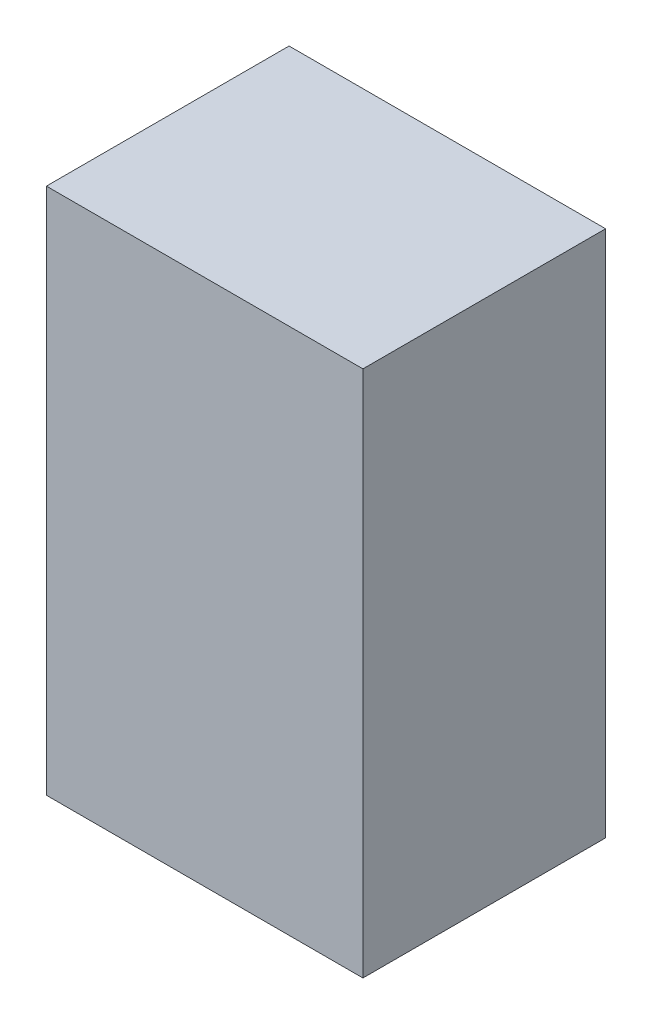
SolidWorks part; units mm, degrees
material "1060 Alloy"
ref_plane "Front Plane" through (0, 0, 0) normal (0, 0, 1) x (1, 0, 0)
ref_plane "Top Plane" through (0, 0, 0) normal (0, 1, 0) x (1, 0, 0)
ref_plane "Right Plane" through (0, 0, 0) normal (1, 0, 0) x (0, 0, -1)
sketch "Sketch1" plane through (0, 0, 0) normal (0, 1, 0) x (1, 0, 0)
  line L0 (-12.5, 9) -> (12.5, 9)
  line L1 (-15, -11.5) -> (15, -11.5)
  line L2 (-15, -11.5) -> (-15, 11.5)
  line L3 (-15, 11.5) -> (15, 11.5)
  line L4 (15, -11.5) -> (15, 11.5)
  line L5 (-15, -11.5) -> (15, 11.5) construction
  line L6 (-15, 11.5) -> (15, -11.5) construction
  line L7 (12.5, -9) -> (12.5, 9)
  line L8 (-12.5, -9) -> (12.5, -9)
  line L9 (-12.5, -9) -> (-12.5, 9)
  point P0 (0, 0)
  dimension "D1" = 30
  dimension "D2" = 23
  dimension "D3" = 2.5
extrude "Boss-Extrude1" add sketch "Sketch1" along normal blind 50 contours L1 L4 L3 L2
extrude "Cut-Extrude2" cut sketch "Sketch1<5>" along normal blind 45 from offset 2.5 contours L9 L8 L7 L0 region at (0, 0, 0)
sketch "Sketch1<5>" plane through (0, 0, 0) normal (0, 1, 0) x (1, 0, 0) same geometry as "Sketch1"
extrude "Boss-Extrude3" add sketch "Sketch1<6>" along normal blind 1 from offset 25 contours L9 L8 L7 L0 region at (0, 0, 0)
sketch "Sketch1<6>" plane through (0, 0, 0) normal (0, 1, 0) x (1, 0, 0) same geometry as "Sketch1"
sketch "Sketch2" plane through (0, 47.5, 0) normal (0, -1, 0) x (-1, 0, 0)
  line L1 (15, -11.5) -> (-15, -11.5) construction
  circle A0 centre (0, -6) radius 2.5
  point P2 (0.5673, -13.5)
  point P3 (0, -8.2634)
  point P7 (0, -7.5)
  dimension "D1" = 5
  dimension "D2" = 5.5
extrude "Cut-Extrude3" cut sketch "Sketch2" against normal up to surface (-47.5 mm away) contours A0 up to face at (0, 0, 0)
sketch "Sketch4" plane through (0, 26, 0) normal (0, 1, 0) x (1, 0, 0)
  line L0 (-12.5, -9) -> (12.5, -9)
  line L1 (-12.5, -9) -> (12.5, -9) construction
  line L2 (-12.5, -9) -> (-12.5, 9) construction
  line L3 (12.5, -9) -> (12.5, -4)
  line L4 (12.5, -9) -> (12.5, 9) construction
  line L5 (12.5, -4) -> (-12.5, -4)
  line L6 (-12.5, -4) -> (-12.5, -9)
  dimension "D1" = 5
extrude "Cut-Extrude4" cut sketch "Sketch4" against normal blind 1
